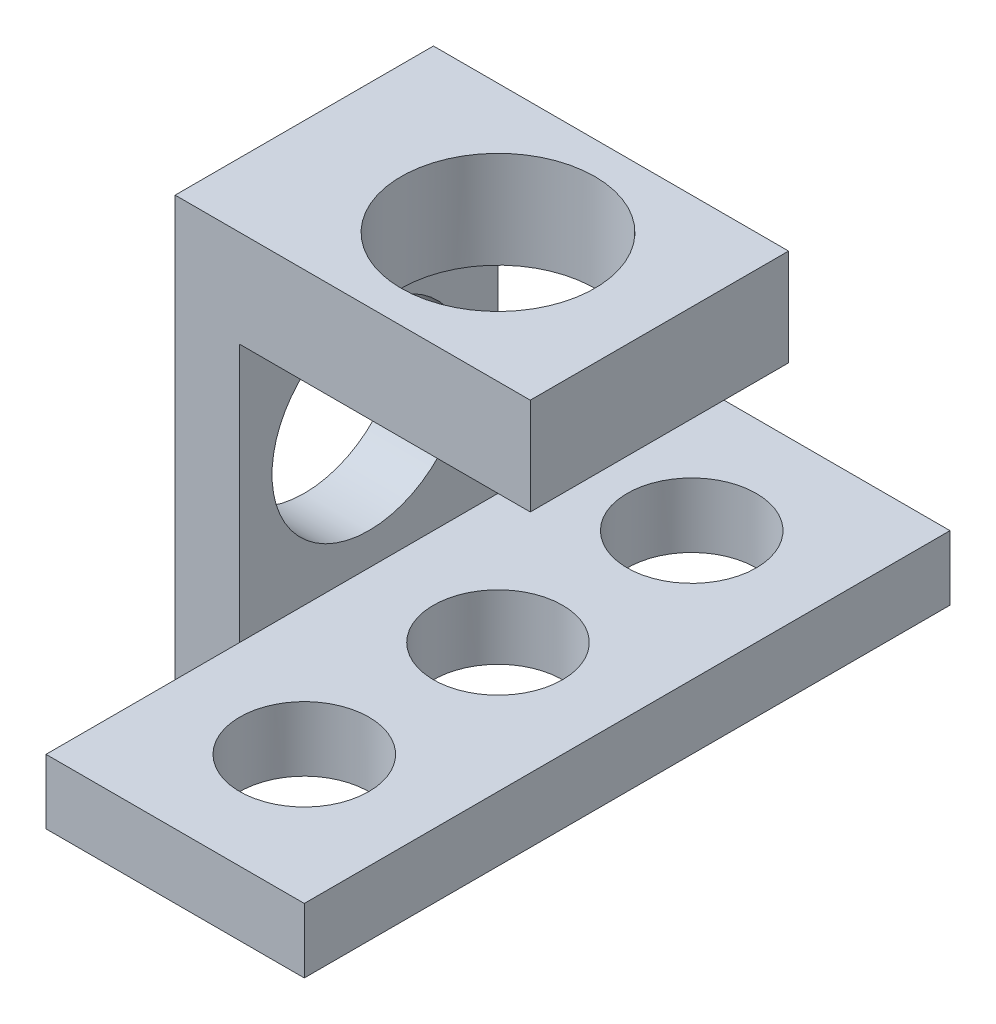
SolidWorks part; units mm, degrees
ref_plane "Front Plane" through (0, 0, 0) normal (0, 0, 1) x (1, 0, 0)
ref_plane "Top Plane" through (0, 0, 0) normal (0, 1, 0) x (1, 0, 0)
ref_plane "Right Plane" through (0, 0, 0) normal (1, 0, 0) x (0, 0, -1)
sketch "Sketch1" plane through (0, 0, 0) normal (0, 0, 1) x (1, 0, 0)
  line L0 (-50, 65) -> (5, 65)
  line L1 (5, 65) -> (5, 50)
  line L2 (5, 50) -> (-40, 50)
  line L3 (-40, 50) -> (-40, 10)
  line L4 (-40, 10) -> (0, 10)
  line L5 (0, 10) -> (0, 0)
  line L6 (0, 0) -> (-50, 0)
  line L7 (-50, 0) -> (-50, 65)
  line L9 (-40, 10) -> (0, 10)
  line L10 (-40, 10) -> (-40, 0)
  line L11 (-40, 0) -> (0, 0)
  line L12 (0, 10) -> (0, 0)
  dimension "D1" = 55
  dimension "D2" = 15
  dimension "D3" = 10
  dimension "D4" = 10
  dimension "D5" = 50
  dimension "D6" = 40
extrude "Boss-Extrude3" add sketch "Sketch1" along normal blind 20 and the other way blind 20 contours L10 L3 L2 L1 L0 L7 L6 region at (-22.5, 64.1485, 0)
extrude "Boss-Extrude4" add sketch "Sketch1<5>" along normal blind 50 and the other way blind 50 contours L4 L10 L6 L5 region at (-20, 5, 0)
sketch "Sketch1<5>" plane through (0, 0, 0) normal (0, 0, 1) x (1, 0, 0) same geometry as "Sketch1"
sketch "Sketch4" plane through (-50, 0, 0) normal (-1, 0, 0) x (0, 0, 1)
  line L0 (20, 0) -> (20, 65) construction
  line L3 (-20, 0) -> (20, 0) construction
  circle A0 centre (0, 30) radius 15
  point P4 (0, 0)
  point P6 (-21.7856, 10)
  dimension "D1" = 30
  dimension "D2" = 20
  dimension "D3" = 30
extrude "Cut-Extrude2" cut sketch "Sketch4" against normal up to next
sketch "Sketch5" plane through (0, 65, 0) normal (0, 1, 0) x (1, 0, 0)
  line L0 (-50, 20) -> (5, 20) construction
  line L1 (-50, 20) -> (-50, -20) construction
  circle A0 centre (-20, 0) radius 15
  dimension "D1" = 30
  dimension "D2" = 20
  dimension "D3" = 30
extrude "Cut-Extrude3" cut sketch "Sketch5" against normal up to next contours A0
sketch "Sketch6" plane through (0, 0, 0) normal (0, -1, 0) x (1, 0, 0)
  line L0 (0, 50) -> (-40, 50) construction
  line L1 (0, -50) -> (0, 50) construction
  circle A0 centre (-20, 30) radius 10
  circle A1 centre (-20, 0) radius 10
  circle A2 centre (-20, -30) radius 10
  point P6 (0, 0)
  point P7 (0, 0)
  point P8 (-19.7687, 30.1466)
  point P9 (0, 0)
  point P11 (-22.4684, 0)
  point P16 (-20, 0)
  dimension "D1" = 30
  dimension "D5" = 20
  dimension "D2" = 30
  dimension "D3" = 50
  dimension "D4" = 20
extrude "Cut-Extrude4" cut sketch "Sketch6" against normal up to next contours A0 | A1 | A2
